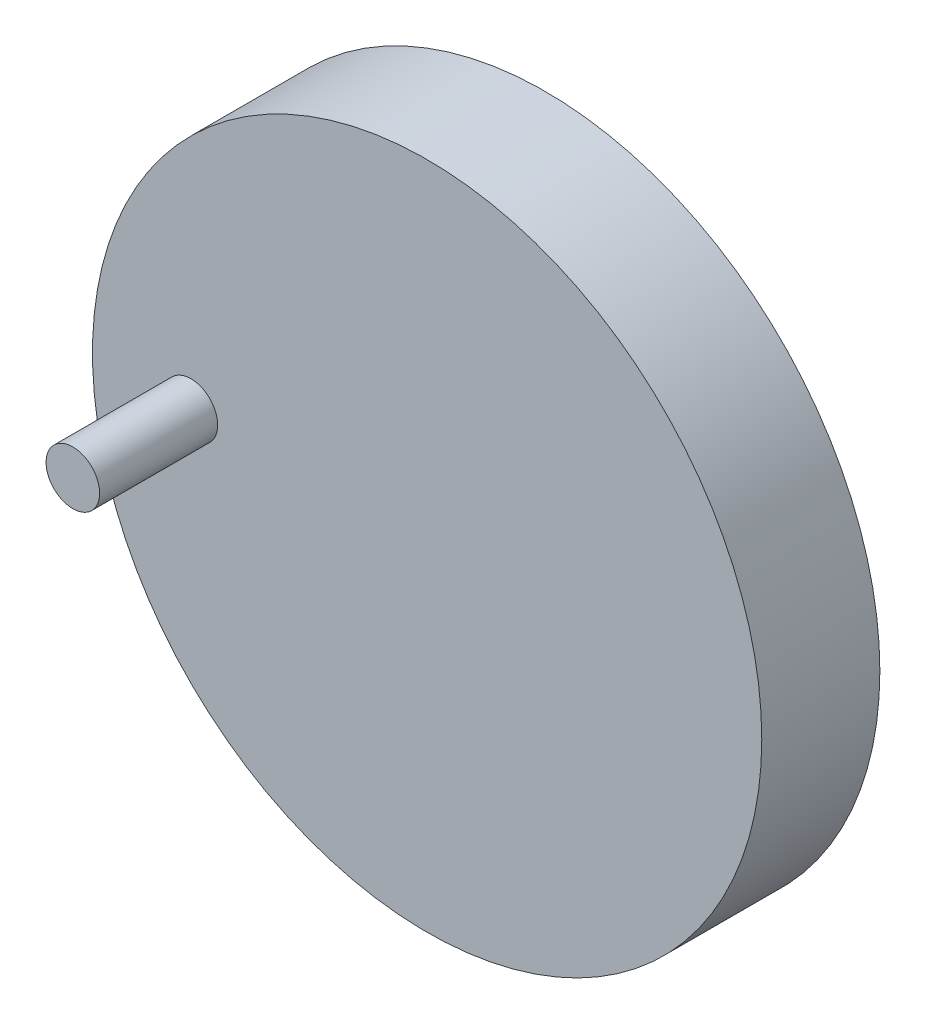
SolidWorks part; units mm, degrees
ref_plane "Front Plane" through (0, 0, 0) normal (0, 0, 1) x (1, 0, 0)
ref_plane "Top Plane" through (0, 0, 0) normal (0, 1, 0) x (1, 0, 0)
ref_plane "Right Plane" through (0, 0, 0) normal (1, 0, 0) x (0, 0, -1)
sketch "Sketch1" plane through (0, 0, 0) normal (0, 0, 1) x (1, 0, 0)
  circle A0 centre (0, 0) radius 28.3375
  circle A1 centre (0, 0) radius 2.267
  circle A2 centre (-20, 0) radius 2.267
  dimension "D1" = 20
extrude "Boss-Extrude1" add sketch "Sketch1" along normal blind 10
extrude "Boss-Extrude2" add sketch "Sketch1<2>" along normal mid plane 20 contours A1
sketch "Sketch1<2>" plane through (0, 0, 0) normal (0, 0, 1) x (1, 0, 0) same geometry as "Sketch1"
extrude "Boss-Extrude3" add sketch "Sketch1<4>" along normal blind 20 contours A2
sketch "Sketch1<4>" plane through (0, 0, 0) normal (0, 0, 1) x (1, 0, 0) same geometry as "Sketch1"
